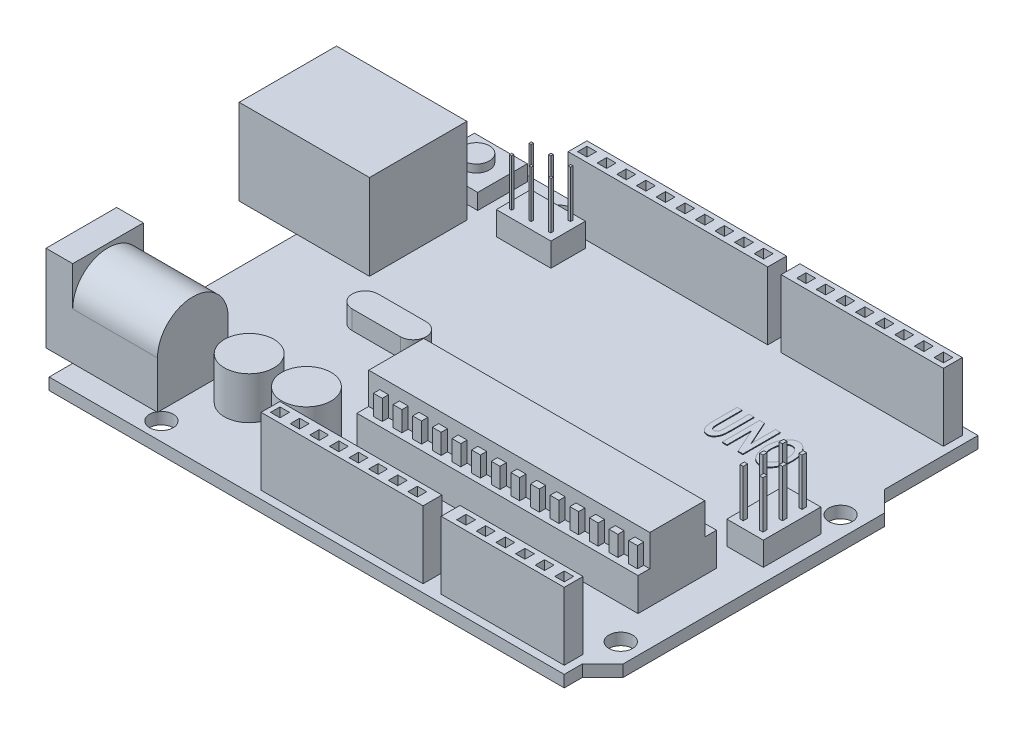
SolidWorks part; units mm, degrees
ref_plane "前基準面" through (0, 0, 0) normal (0, 0, 1) x (1, 0, 0)
ref_plane "上基準面" through (0, 0, 0) normal (0, 1, 0) x (1, 0, 0)
ref_plane "右基準面" through (0, 0, 0) normal (1, 0, 0) x (0, 0, -1)
sketch "草圖1" plane through (0, 0, 0) normal (0, 1, 0) x (1, 0, 0)
  line L0 (25.2641, 24.6244) -> (27.8641, 22.0244)
  line L1 (-40.3359, 36.5244) -> (25.2641, 36.5244)
  line L2 (-40.3359, 36.5244) -> (-40.3359, -16.1756)
  line L3 (-40.3359, -16.1756) -> (25.2641, -16.1756)
  line L4 (25.2641, 36.5244) -> (25.2641, 24.6244)
  line L5 (27.8641, 22.0244) -> (27.8641, -11.2756)
  line L6 (27.8641, -11.2756) -> (25.2641, -13.8756)
  line L7 (25.2641, -13.8756) -> (25.2641, -16.1756)
  line L8 (25.2641, 19.0244) -> (25.2641, -8.9756) construction
  circle A0 centre (25.2641, 19.0244) radius 1.5
  circle A1 centre (25.2641, -8.9756) radius 1.5
  circle A2 centre (-25.7359, 34.2244) radius 1.5
  circle A3 centre (-28.3359, -13.8756) radius 1.5
  dimension "D8" = 3
  dimension "D9" = 3
  dimension "D10" = 1.1
  dimension "D12" = 16
  dimension "D13" = 0.8
  dimension "D14" = 0.8
  dimension "D15" = 13.1
  dimension "D16" = 3
  dimension "D17" = 12
  dimension "D18" = 3
  dimension "D1" = 52.7
  dimension "D2" = 65.6
  dimension "D3" = 2.6
  dimension "D4" = 2.3
  dimension "D5" = 135
  dimension "D6" = 11.9
  dimension "D7" = 135
  dimension "D11" = 28
extrude "填料-伸長1" add sketch "草圖1" along normal blind 1.5
sketch "草圖2" plane through (0, 1.5, 0) normal (0, 1, 0) x (1, 0, 0)
  line L0 (-40.3359, 36.5244) -> (-40.3359, -16.1756) construction
  line L1 (-47.6359, 27.7244) -> (-31.0359, 27.7244)
  line L2 (-47.6359, 27.7244) -> (-47.6359, 15.3244)
  line L3 (-47.6359, 15.3244) -> (-31.0359, 15.3244)
  line L4 (-31.0359, 27.7244) -> (-31.0359, 15.3244)
  line L5 (25.2641, 36.5244) -> (-40.3359, 36.5244) construction
  dimension "D1" = 16.6
  dimension "D2" = 12.4
  dimension "D3" = 7.3
  dimension "D4" = 8.8
extrude "填料-伸長2" add sketch "草圖2" along normal blind 10.9
sketch "草圖3" plane through (-47.6359, 0, 0) normal (-1, 0, 0) x (0, 0, 1)
  line L0 (-24.4011, 11.3216) -> (-18.6505, 11.3216)
  line L1 (-23.7422, 8.3265) -> (-19.3694, 8.3265)
  line L2 (-23.7422, 8.3265) -> (-23.7422, 6.2899)
  line L3 (-23.7422, 6.2899) -> (-19.3694, 6.2899)
  line L4 (-19.3694, 8.3265) -> (-19.3694, 6.2899)
  line L5 (-18.6505, 11.3216) -> (-16.4042, 9.0753)
  line L6 (-16.4042, 9.0753) -> (-16.4042, 2.8155)
  line L7 (-16.4042, 2.8155) -> (-26.6774, 2.8155)
  line L8 (-26.6774, 2.8155) -> (-26.6774, 9.0753)
  line L9 (-26.6774, 9.0753) -> (-24.4011, 11.3216)
extrude "除料-伸長1" cut sketch "草圖3" against normal blind 10.9
sketch "草圖4" plane through (0, 1.5, 0) normal (0, 1, 0) x (1, 0, 0)
  line L1 (-38.148, 35.7984) -> (-31.4042, 35.7984)
  line L2 (-38.148, 35.7984) -> (-38.148, 29.4753)
  line L3 (-38.148, 29.4753) -> (-31.4042, 29.4753)
  line L4 (-31.4042, 35.7984) -> (-31.4042, 29.4753)
extrude "填料-伸長3" add sketch "草圖4" along normal blind 2
sketch "草圖5" plane through (0, 3.5, 0) normal (0, 1, 0) x (1, 0, 0)
  circle A0 centre (-34.7975, 32.6949) radius 1.6646
extrude "填料-伸長4" add sketch "草圖5" along normal blind 1
sketch "草圖6" plane through (0, 1.5, 0) normal (0, 1, 0) x (1, 0, 0)
  line L0 (25.2641, 36.5244) -> (-40.3359, 36.5244) construction
  line L1 (-23.5359, 35.5244) -> (24.2641, 35.5244)
  line L2 (-23.5359, 35.5244) -> (-23.5359, 33.1244)
  line L3 (-23.5359, 33.1244) -> (24.2641, 33.1244)
  line L4 (24.2641, 35.5244) -> (24.2641, 33.1244)
  line L5 (25.2641, 24.6244) -> (25.2641, 36.5244) construction
  line L6 (25.2641, -16.1756) -> (25.2641, -13.8756) construction
  line L7 (24.2641, -15.1756) -> (-14.3359, -15.1756)
  line L8 (24.2641, -15.1756) -> (24.2641, -12.7756)
  line L9 (24.2641, -12.7756) -> (-14.3359, -12.7756)
  line L10 (-14.3359, -15.1756) -> (-14.3359, -12.7756)
  line L11 (-40.3359, -16.1756) -> (25.2641, -16.1756) construction
  dimension "D1" = 47.8
  dimension "D2" = 2.4
  dimension "D3" = 1
  dimension "D4" = 1
  dimension "D5" = 2.4
  dimension "D6" = 38.6
  dimension "D7" = 1
  dimension "D8" = 1
extrude "填料-伸長5" add sketch "草圖6" along normal blind 8.6
sketch "草圖7" plane through (0, 1.5, 0) normal (0, 1, 0) x (1, 0, 0)
  line L0 (27.8641, -11.2756) -> (27.8641, 22.0244) construction
  line L1 (-12.5359, 5.2244) -> (23.2641, 5.2244)
  line L2 (-12.5359, 5.2244) -> (-12.5359, -4.7756)
  line L3 (-12.5359, -4.7756) -> (23.2641, -4.7756)
  line L4 (23.2641, 5.2244) -> (23.2641, -4.7756)
  line L5 (24.2641, -12.7756) -> (-14.3359, -12.7756) construction
  dimension "D1" = 4.6
  dimension "D2" = 10
  dimension "D3" = 35.8
  dimension "D4" = 8
extrude "填料-伸長6" add sketch "草圖7" along normal blind 8.2
sketch "草圖8" plane through (0, 1.5, 0) normal (0, 1, 0) x (1, 0, 0)
  line L0 (-24.7753, -6.2598) -> (-17.4808, -6.2598) construction
  line L1 (-26.1439, 9.8798) -> (-20.0177, 9.8798) construction
  line L2 (-26.1439, 11.5292) -> (-20.0177, 11.5292)
  line L3 (-26.1439, 8.2305) -> (-20.0177, 8.2305)
  circle A0 centre (-24.7753, -6.2598) radius 3.15
  circle A1 centre (-17.4808, -6.2598) radius 3.15
  arc A2 (-26.1439, 11.5292) -> (-26.1439, 8.2305) centre (-26.1439, 9.8798) ccw
  arc A3 (-20.0177, 8.2305) -> (-20.0177, 11.5292) centre (-20.0177, 9.8798) ccw
  point P6 (-23.0808, 9.8798)
  dimension "D1" = 6.3
  dimension "D2" = 6.3
extrude "填料-伸長7" add sketch "草圖8" along normal blind 5.4
sketch "草圖9" plane through (0, 10.1, 0) normal (0, 1, 0) x (1, 0, 0)
  line L0 (-23.5359, 33.1244) -> (24.2641, 33.1244) construction
  line L1 (23.6641, 34.9244) -> (22.4641, 34.9244)
  line L2 (23.6641, 34.9244) -> (23.6641, 33.7244)
  line L3 (23.6641, 33.7244) -> (22.4641, 33.7244)
  line L4 (22.4641, 34.9244) -> (22.4641, 33.7244)
  line L5 (24.2641, 33.1244) -> (24.2641, 35.5244) construction
  dimension "D1" = 1.2
  dimension "D2" = 1.2
  dimension "D3" = 0.6
  dimension "D4" = 0.6
extrude "除料-伸長2" cut sketch "草圖9" against normal blind 5.4
pattern_linear "直線複製排列1" count 8 spacing 2.5 along (-1, 0, 0) of "除料-伸長2"
sketch "草圖10" plane through (0, 10.1, 0) normal (0, 1, 0) x (1, 0, 0)
  line L0 (-23.5359, 33.1244) -> (24.2641, 33.1244) construction
  line L1 (-22.9359, 34.9244) -> (-21.7359, 34.9244)
  line L2 (-22.9359, 34.9244) -> (-22.9359, 33.7244)
  line L3 (-22.9359, 33.7244) -> (-21.7359, 33.7244)
  line L4 (-21.7359, 34.9244) -> (-21.7359, 33.7244)
  line L5 (-23.5359, 35.5244) -> (-23.5359, 33.1244) construction
  dimension "D1" = 1.2
  dimension "D2" = 1.2
  dimension "D3" = 0.6
  dimension "D4" = 0.6
extrude "除料-伸長3" cut sketch "草圖10" against normal blind 5.4
pattern_linear "直線複製排列2" count 10 spacing 2.5 along (1, 0, 0) of "除料-伸長3"
sketch "草圖11" plane through (0, 10.1, 0) normal (0, 1, 0) x (1, 0, 0)
  line L0 (-14.3359, -15.1756) -> (24.2641, -15.1756) construction
  line L1 (23.6641, -13.3756) -> (22.4641, -13.3756)
  line L2 (23.6641, -13.3756) -> (23.6641, -14.5756)
  line L3 (23.6641, -14.5756) -> (22.4641, -14.5756)
  line L4 (22.4641, -13.3756) -> (22.4641, -14.5756)
  line L5 (24.2641, -15.1756) -> (24.2641, -12.7756) construction
  dimension "D1" = 1.2
  dimension "D2" = 1.2
  dimension "D3" = 0.6
  dimension "D4" = 0.6
extrude "除料-伸長4" cut sketch "草圖11" against normal blind 5.4
pattern_linear "直線複製排列3" count 6 spacing 2.5 along (-1, 0, 0) of "除料-伸長4"
sketch "草圖12" plane through (0, 10.1, 0) normal (0, 1, 0) x (1, 0, 0)
  line L0 (-14.3359, -15.1756) -> (24.2641, -15.1756) construction
  line L1 (-13.7359, -13.3756) -> (-12.5359, -13.3756)
  line L2 (-13.7359, -13.3756) -> (-13.7359, -14.5756)
  line L3 (-13.7359, -14.5756) -> (-12.5359, -14.5756)
  line L4 (-12.5359, -13.3756) -> (-12.5359, -14.5756)
  line L5 (-14.3359, -12.7756) -> (-14.3359, -15.1756) construction
  dimension "D1" = 1.2
  dimension "D2" = 1.2
  dimension "D3" = 0.6
  dimension "D4" = 0.6
extrude "除料-伸長5" cut sketch "草圖12" against normal blind 5.4
pattern_linear "直線複製排列4" count 8 spacing 2.5 along (1, 0, 0) of "除料-伸長5"
sketch "草圖13" plane through (-40.3359, 0, 0) normal (-1, 0, 0) x (0, 0, 1)
  line L0 (-15.3244, 1.5) -> (16.1756, 1.5) construction
  line L1 (13.1756, 1.5) -> (4.1756, 1.5)
  line L2 (13.1756, 1.5) -> (13.1756, 12.5)
  line L3 (13.1756, 12.5) -> (4.1756, 12.5)
  line L4 (4.1756, 1.5) -> (4.1756, 12.5)
  line L5 (16.1756, 1.5) -> (16.1756, 0) construction
  dimension "D1" = 11
  dimension "D2" = 9
  dimension "D3" = 3
extrude "填料-伸長8" add sketch "草圖13" along normal blind 3.4 separate body
sketch "草圖14" plane through (-40.3359, 0, 0) normal (1, 0, 0) x (0, 0, -1)
  line L0 (-13.1756, 7.5) -> (-13.1756, 1.5)
  line L1 (-4.1756, 1.5) -> (-13.1756, 1.5) construction
  line L2 (-13.1756, 1.5) -> (-4.1756, 1.5)
  line L3 (-11.2756, 1.5) -> (22.0244, 1.5) construction
  line L4 (-4.1756, 1.5) -> (-4.1756, 7.5)
  line L5 (-13.1756, 1.5) -> (-13.1756, 12.5) construction
  line L6 (15.3244, 1.5) -> (-16.1756, 1.5) construction
  arc A0 (-4.1756, 7.5) -> (-13.1756, 7.5) centre (-8.6756, 7.5) ccw
  dimension "D1" = 4.5
  dimension "D2" = 6
extrude "填料-伸長9" add sketch "草圖14" along normal blind 10.8
sketch "草圖15" plane through (-43.7359, 0, 0) normal (-1, 0, 0) x (0, 0, 1)
  circle A0 centre (8.6756, 7.5) radius 3.8845
  circle A1 centre (8.6756, 7.5) radius 0.4076
extrude "除料-伸長6" cut sketch "草圖15" against normal blind 10.8
sketch "草圖16" plane through (0, 9.7, 0) normal (0, 1, 0) x (1, 0, 0)
  line L0 (23.2641, -4.7756) -> (23.2641, 5.2244) construction
  line L1 (-12.5359, 5.2244) -> (23.2641, 5.2244)
  line L2 (-12.5359, 5.2244) -> (-12.5359, 3.7244)
  line L3 (-12.5359, 3.7244) -> (23.2641, 3.7244)
  line L4 (23.2641, 5.2244) -> (23.2641, 3.7244)
  line L6 (-12.5359, -4.7756) -> (23.2641, -4.7756)
  line L7 (-12.5359, -4.7756) -> (-12.5359, -3.2756)
  line L8 (-12.5359, -3.2756) -> (23.2641, -3.2756)
  line L9 (23.2641, -4.7756) -> (23.2641, -3.2756)
  dimension "D1" = 1.5
  dimension "D2" = 1.5
extrude "除料-伸長7" cut sketch "草圖16" against normal blind 4
sketch "草圖17" plane through (0, 0, 3.2756) normal (0, 0, 1) x (1, 0, 0)
  line L0 (23.2641, 5.7) -> (-12.5359, 5.7) construction
  line L1 (21.3731, 8.261) -> (22.4916, 8.261)
  line L2 (21.3731, 8.261) -> (21.3731, 5.7)
  line L3 (21.3731, 5.7) -> (22.4916, 5.7)
  line L4 (22.4916, 8.261) -> (22.4916, 5.7)
extrude "填料-伸長10" add sketch "草圖17" along normal blind 0.8
pattern_linear "直線複製排列5" count 14 spacing 2.5 along (-1, 0, 0) of "填料-伸長10"
sketch "草圖18" plane through (0, 0, -3.7244) normal (0, 0, -1) x (-1, 0, 0)
  line L1 (-21.3731, 8.261) -> (-22.4916, 8.261)
  line L2 (-21.3731, 8.261) -> (-21.3731, 5.7)
  line L3 (-21.3731, 5.7) -> (-22.4916, 5.7)
  line L4 (-22.4916, 8.261) -> (-22.4916, 5.7)
extrude "填料-伸長11" add sketch "草圖18" along normal blind 0.8
pattern_linear "直線複製排列6" count 14 spacing 2.5 along (-1, 0, 0) of "填料-伸長11"
sketch "草圖19" plane through (0, 10.1, 0) normal (0, 1, 0) x (1, 0, 0)
  line L0 (24.2641, -12.7756) -> (-14.3359, -12.7756) construction
  line L1 (6.287, -12.7756) -> (8.5909, -12.7756)
  line L2 (6.287, -12.7756) -> (6.287, -15.1756)
  line L3 (6.287, -15.1756) -> (8.5909, -15.1756)
  line L4 (8.5909, -12.7756) -> (8.5909, -15.1756)
  line L5 (-14.3359, -15.1756) -> (24.2641, -15.1756) construction
  line L6 (24.2641, 35.5244) -> (-23.5359, 35.5244) construction
  line L7 (1.8829, 35.5244) -> (3.5883, 35.5244)
  line L8 (1.8829, 35.5244) -> (1.8829, 33.1244)
  line L9 (1.8829, 33.1244) -> (3.5883, 33.1244)
  line L10 (3.5883, 35.5244) -> (3.5883, 33.1244)
  line L11 (-23.5359, 33.1244) -> (24.2641, 33.1244) construction
extrude "除料-伸長8" cut sketch "草圖19" against normal up to surface (8.6 mm away) up to face at (-23.0808, 1.5, -9.8798)
sketch "草圖20" plane through (0, 1.5, 0) normal (0, 1, 0) x (1, 0, 0)
  line L1 (26.1424, 15.6221) -> (21.4933, 15.6221)
  line L2 (26.1424, 15.6221) -> (26.1424, 8.3036)
  line L3 (26.1424, 8.3036) -> (21.4933, 8.3036)
  line L4 (21.4933, 15.6221) -> (21.4933, 8.3036)
  line L5 (-27.3258, 32.1564) -> (-20.3705, 32.1564)
  line L6 (-27.3258, 32.1564) -> (-27.3258, 27.7655)
  line L7 (-27.3258, 27.7655) -> (-20.3705, 27.7655)
  line L8 (-20.3705, 32.1564) -> (-20.3705, 27.7655)
extrude "填料-伸長12" add sketch "草圖20" along normal blind 3
sketch "草圖21" plane through (0, 4.5, 0) normal (0, 1, 0) x (1, 0, 0)
  line L1 (22.3105, 14.7152) -> (22.7281, 14.7152)
  line L2 (22.3105, 14.7152) -> (22.3105, 14.1584)
  line L3 (22.3105, 14.1584) -> (22.7281, 14.1584)
  line L4 (22.7281, 14.7152) -> (22.7281, 14.1584)
extrude "填料-伸長13" add sketch "草圖21" along normal blind 6
pattern_linear "直線複製排列7" count 2 spacing 2.5 along (1, 0, 0) count 3 spacing 2.5 along (0, 0, 1) of "填料-伸長13"
sketch "草圖22" plane through (0, 4.5, 0) normal (0, 1, 0) x (1, 0, 0)
  line L1 (-26.5592, 31.4655) -> (-26.2729, 31.4655)
  line L2 (-26.5592, 31.4655) -> (-26.5592, 31.1571)
  line L3 (-26.5592, 31.1571) -> (-26.2729, 31.1571)
  line L4 (-26.2729, 31.4655) -> (-26.2729, 31.1571)
extrude "填料-伸長14" add sketch "草圖22" along normal blind 6
pattern_linear "直線複製排列8" count 3 spacing 2.5 along (1, 0, 0) count 2 spacing 2.5 along (0, 0, 1) of "填料-伸長14"
sketch "草圖23" plane through (0, 6.9, 0) normal (0, 1, 0) x (1, 0, 0)
  line L2 (-26.1439, 8.2305) -> (-20.0177, 8.2305)
  line L3 (-20.0177, 11.5292) -> (-26.1439, 11.5292)
  line L4 (-26.1439, 8.2305) -> (-20.0177, 8.2305)
  line L5 (-20.0177, 11.5292) -> (-26.1439, 11.5292)
  arc A2 (-26.1439, 11.5292) -> (-26.1439, 8.2305) centre (-26.1439, 9.8798) ccw
  arc A3 (-20.0177, 8.2305) -> (-20.0177, 11.5292) centre (-20.0177, 9.8798) ccw
  arc A4 (-26.1439, 11.5292) -> (-26.1439, 8.2305) centre (-26.1439, 9.8798) ccw
  arc A5 (-20.0177, 8.2305) -> (-20.0177, 11.5292) centre (-20.0177, 9.8798) ccw
  dimension "D1" = 0
extrude "除料-伸長9" cut sketch "草圖23" against normal blind 3
sketch "草圖24" plane through (0, 1.5, 0) normal (0, 1, 0) x (1, 0, 0)
  text T0 "<b>UNO</b>" font "Century Gothic" height in points 18
extrude "填料-伸長15" add sketch "草圖24" along normal blind 0.1
